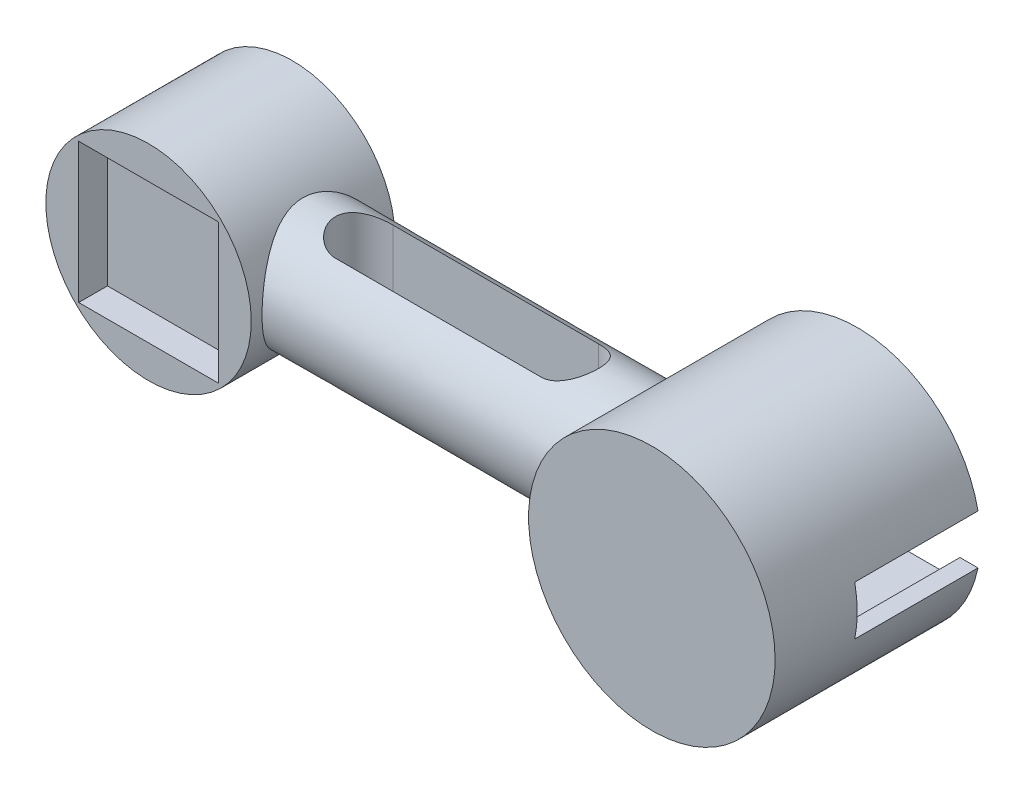
SolidWorks part; units mm, degrees
ref_plane "Front Plane" through (0, 0, 0) normal (0, 0, 1) x (1, 0, 0)
ref_plane "Top Plane" through (0, 0, 0) normal (0, 1, 0) x (1, 0, 0)
ref_plane "Right Plane" through (0, 0, 0) normal (1, 0, 0) x (0, 0, -1)
sketch "Sketch1" plane through (0, 0, 0) normal (0, 0, 1) x (1, 0, 0)
  circle A0 centre (0, 0) radius 25
  dimension "D1" = 50
extrude "Boss-Extrude1" add sketch "Sketch1" along normal mid plane 35
sketch "Sketch2" plane through (0, 0, 0) normal (1, 0, 0) x (0, 0, -1)
  circle A0 centre (0, 0) radius 15
  dimension "D1" = 30
ref_plane "Plane1" through (130, 0, 0) normal (1, 0, 0) x (0, 0, -1)
sketch "Sketch3" plane through (130, 0, 0) normal (1, 0, 0) x (0, 0, -1)
  circle A0 centre (0, 0) radius 15
  dimension "D1" = 30
loft "Loft1" add profiles "Sketch2", "Sketch3" connector at (0, 9.43, -11.6651) connector at (130, 5.0545, -14.1228)
sketch "Sketch4" plane through (0, 0, 0) normal (0, 0, 1) x (1, 0, 0)
  line L0 (130, -19.25) -> (130, 19.25) construction
  circle A0 centre (130, 0) radius 30
  dimension "D1" = 60
extrude "Boss-Extrude2" add sketch "Sketch4" along normal mid plane 50
sketch "Sketch5" plane through (0, 0, 0) normal (0, 1, 0) x (1, 0, 0)
  line L0 (35, 0) -> (85, 0) construction
  line L1 (35, 7) -> (85, 7)
  line L2 (35, -7) -> (85, -7)
  arc A0 (35, 7) -> (35, -7) centre (35, 0) ccw
  arc A1 (85, -7) -> (85, 7) centre (85, 0) ccw
  point P3 (60, 0)
  point P8 (63.858, 0)
  dimension "D3" = 7
  dimension "D1" = 50
  dimension "D2" = 60
extrude "Cut-Extrude1" cut sketch "Sketch5" against normal through all both and the other way through all
sketch "Sketch6" plane through (0, 0, 17.5) normal (0, 0, 1) x (1, 0, 0)
  line L1 (17, -17) -> (-17, -17)
  line L2 (17, -17) -> (17, 17)
  line L3 (17, 17) -> (-17, 17)
  line L4 (-17, -17) -> (-17, 17)
  line L5 (17, -17) -> (-17, 17) construction
  line L6 (17, 17) -> (-17, -17) construction
  point P0 (0, 0)
  dimension "D1" = 34
  dimension "D2" = 34
extrude "Cut-Extrude2" cut sketch "Sketch6" against normal blind 7
sketch "Sketch7" plane through (0, 0, -17.5) normal (0, 0, -1) x (-1, 0, 0)
  circle A0 centre (0, 0) radius 3.9
  dimension "D1" = 7.8
extrude "Boss-Extrude3" add sketch "Sketch7" along normal blind 7 draft 2
sketch "Sketch8" plane through (0, 0, -25) normal (0, 0, -1) x (-1, 0, 0)
  line L0 (-130, 27.5) -> (-130, -27.5) construction
  line L1 (-113, -11) -> (-155, -11)
  line L2 (-113, -11) -> (-113, 11)
  line L3 (-113, 11) -> (-155, 11)
  line L4 (-155, -11) -> (-155, 11)
  line L5 (-113, -11) -> (-155, 11) construction
  line L6 (0, 0) -> (40.2637, 0) construction
  line L8 (-155, -6) -> (-165, -6)
  line L9 (-155, -6) -> (-155, 6)
  line L10 (-155, 6) -> (-165, 6)
  line L11 (-165, -6) -> (-165, 6)
  line L12 (-155, -6) -> (-165, 6) construction
  line L13 (-155, 6) -> (-165, -6) construction
  circle A0 centre (-130, 0) radius 30 construction
  point P0 (-143, 4.7143)
  point P7 (-160, 0)
  point P17 (0, 0)
  circle M10 centre (-130, 0) radius 30
  dimension "D1" = 13
  dimension "D2" = 22
  dimension "D3" = 30
  dimension "D4" = 42
  dimension "D5" = 12
extrude "Cut-Extrude3" cut sketch "Sketch8" against normal blind 30 contours L4 L1 L2 L3 | L11 L8 L10 M10 | L4 L10 L8 M10 region at (134, 0, -25) region at (157.4028, 0, -25) region at (162.3963, 0, -25)
